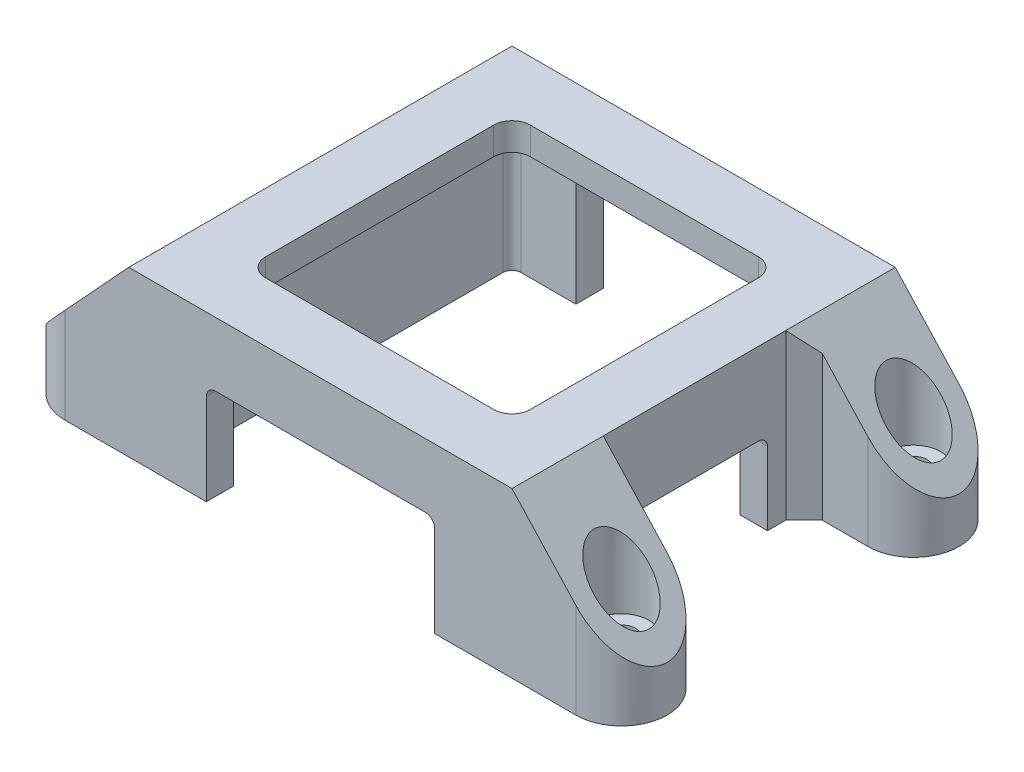
SolidWorks part; units mm, degrees
ref_plane "Front Plane" through (0, 0, 0) normal (0, 0, 1) x (1, 0, 0)
ref_plane "Top Plane" through (0, 0, 0) normal (0, 1, 0) x (1, 0, 0)
ref_plane "Right Plane" through (0, 0, 0) normal (1, 0, 0) x (0, 0, -1)
sketch "Sketch1" plane through (0, 0, 0) normal (0, 1, 0) x (1, 0, 0)
  line L5 (-18, -18) -> (18, -18)
  line L6 (-18, -18) -> (-18, 18)
  line L7 (-18, 18) -> (18, 18)
  line L8 (18, -18) -> (18, 18)
  line L9 (-18, -18) -> (18, 18) construction
  line L10 (-18, 18) -> (18, -18) construction
  point P0 (0, 0)
  dimension "D1" = 36
extrude "Boss-Extrude1" add sketch "Sketch1" along normal blind 15
shell "Shell1" thickness 3 removed face at (0, 0, 0) outward yes
sketch "Sketch2" plane through (0, 0, 21) normal (0, 0, 1) x (1, 0, 0)
  line L1 (-12.5, 0) -> (12.5, 0)
  line L2 (-12.5, 0) -> (-12.5, 11)
  line L3 (-12.5, 11) -> (12.5, 11)
  line L4 (12.5, 0) -> (12.5, 11)
  line L5 (-12.5, 11) -> (12.5, 0) construction
  line L6 (-21, 0) -> (21, 0) construction
  point P4 (0, 5.8702)
  point P6 (0, 5.5)
  point P7 (0, 0)
  dimension "D1" = 11
  dimension "D2" = 25
extrude "Cut-Extrude1" cut sketch "Sketch2" against normal up to next
sketch "Sketch3" plane through (21, 0, 0) normal (1, 0, 0) x (0, 0, -1)
  line L1 (-11, 0) -> (7, 0)
  line L2 (-11, 0) -> (-11, 9)
  line L3 (-11, 9) -> (7, 9)
  line L4 (7, 0) -> (7, 9)
  line L6 (-21, 18) -> (-21, 0) construction
  line L7 (-21, 0) -> (21, 0) construction
  dimension "D1" = 18
  dimension "D2" = 9
  dimension "D3" = 10
extrude "Cut-Extrude2" cut sketch "Sketch3" against normal up to next
sketch "Sketch5" plane through (0, 18, 0) normal (0, 1, 0) x (1, 0, 0)
  line L5 (-14.5, -14.5) -> (14.5, -14.5)
  line L6 (-14.5, -14.5) -> (-14.5, 14.5)
  line L7 (-14.5, 14.5) -> (14.5, 14.5)
  line L8 (14.5, -14.5) -> (14.5, 14.5)
  line L9 (-14.5, -14.5) -> (14.5, 14.5) construction
  line L10 (-14.5, 14.5) -> (14.5, -14.5) construction
  point P3 (0, 0)
  dimension "D1" = 29
extrude "Cut-Extrude3" cut sketch "Sketch5" against normal up to next
fillet "Fillet1" radius 2 4 edges at (-14.5, 16.5, 14.5) (14.5, 16.5, 14.5) (14.5, 16.5, -14.5) (-14.5, 16.5, -14.5)
sketch "Sketch6" plane through (0, 0, -21) normal (0, 0, -1) x (-1, 0, 0)
  line L1 (-11, 0) -> (11, 0)
  line L2 (-11, 0) -> (-11, 14)
  line L3 (-11, 14) -> (11, 14)
  line L4 (11, 0) -> (11, 14)
  line L5 (-11, 14) -> (11, 0) construction
  line L6 (-21, 0) -> (21, 0) construction
  point P6 (0, 7)
  point P7 (0, 0)
  dimension "D1" = 22
  dimension "D2" = 14
extrude "Cut-Extrude4" cut sketch "Sketch6" against normal up to next
fillet "Fillet2" radius 1 6 edges at (-11, 14, -19.5) (11, 14, -19.5) (19.5, 9, -7) (19.5, 9, 11) (12.5, 11, 19.5) (-12.5, 11, 19.5)
sketch "Sketch9" plane through (0, 0, 0) normal (0, -1, 0) x (1, 0, 0)
  line L1 (-21, 21) -> (-33, 21)
  line L2 (-21, 21) -> (-21, 11)
  line L3 (-21, 11) -> (-33, 11)
  line L4 (-33, 21) -> (-33, 11)
  dimension "D1" = 10
  dimension "D2" = 12
extrude "Boss-Extrude3" add sketch "Sketch9" against normal blind 5
sketch "Sketch10" plane through (0, 0, 21) normal (0, 0, 1) x (1, 0, 0)
  line L0 (-21, 18) -> (-33, 5)
  line L1 (-33, 5) -> (-21, 5)
  line L2 (-21, 5) -> (-21, 18)
extrude "Boss-Extrude4" add sketch "Sketch10" against normal up to surface (10 mm away) up to face at (-27, 2.5, 11)
sketch "Sketch11" plane through (0, 0, 0) normal (0, -1, 0) x (1, 0, 0)
  line L0 (-33, 21) -> (-33, 11) construction
  line L1 (-33, 21) -> (-12.5, 21) construction
  circle A0 centre (-28, 16) radius 1.5
  point P4 (-33, 16)
  dimension "D1" = 3
  dimension "D2" = 5
  dimension "D3" = 5
extrude "Cut-Extrude5" cut sketch "Sketch11" against normal blind 5
sketch "Sketch12" plane through (0, 5, 0) normal (0, -1, 0) x (1, 0, 0)
  circle A0 centre (-28, 16) radius 3
  dimension "D1" = 6
extrude "Cut-Extrude6" cut sketch "Sketch12" against normal up to next contours A0
sketch "Sketch13" plane through (0, 0, 0) normal (0, -1, 0) x (1, 0, 0)
  circle A0 centre (-28, 16) radius 5
  point P3 (-28, 16)
  line M8 (-12.5, 21) -> (-33, 21)
  line M9 (-33, 21) -> (-33, 11)
  line M10 (-33, 11) -> (-21, 11)
  dimension "D1" = 10
extrude "Cut-Extrude7" cut sketch "Sketch13" against normal up to next contours A0 M8 M9 | A0 M9 M10 region at (-31.8832, 0, 19.8832) region at (-31.8832, 0, 12.1168)
mirror "Mirror1" about plane through (0, 0, 0) normal (0, 0, 1) of "Boss-Extrude4", "Boss-Extrude3", "Cut-Extrude7", "Cut-Extrude6", "Cut-Extrude5"
mirror "Mirror3" about plane through (0, 0, 0) normal (1, 0, 0) of "Mirror1"
chamfer "Chamfer1" distance 2 angle 45 3 edges at (21, 9, -11) (-21, 9, 11) (-21, 9, -11)
fillet "Fillet3" radius 1 4 edges at (18, 7.5, -18) (-18, 7.5, 18) (18, 7.5, 18) (-18, 7.5, -18)
